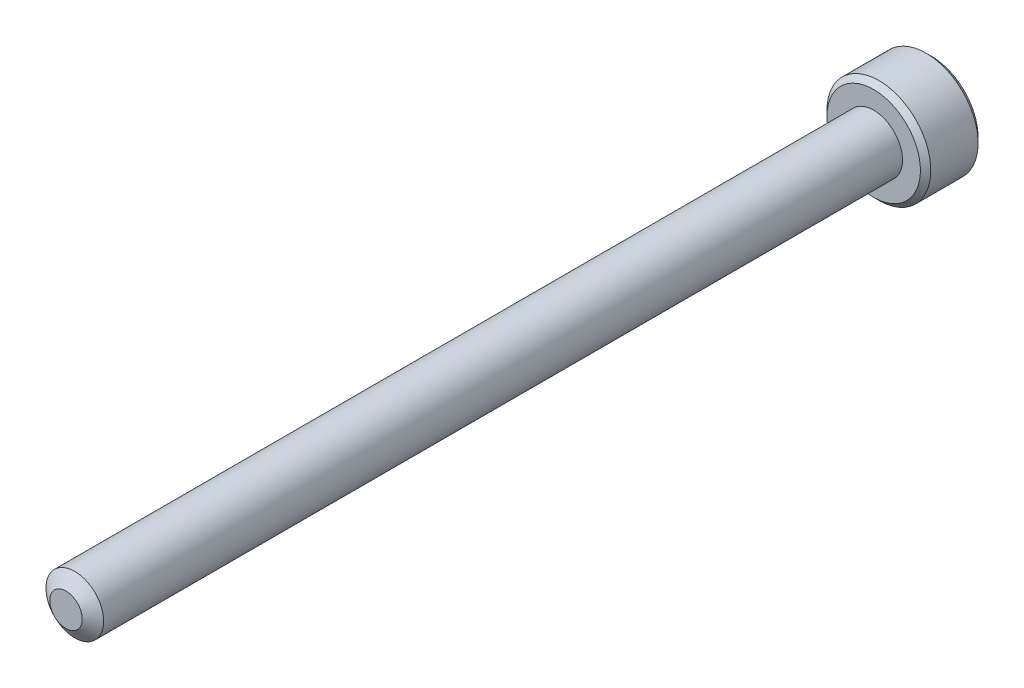
SolidWorks part; units mm, degrees
other "DetailItem1"
ref_plane "Front Plane" through (0, 0, 0) normal (0, 0, 1) x (1, 0, 0)
ref_plane "Top Plane" through (0, 0, 0) normal (0, 1, 0) x (1, 0, 0)
ref_plane "Right Plane" through (0, 0, 0) normal (1, 0, 0) x (0, 0, -1)
sketch "Sketch1" plane through (0, 0, 0) normal (0, 0, 1) x (1, 0, 0)
  circle A0 centre (0, 0) radius 1.25
  dimension "OD" = 2.5
extrude "Extrude1" add sketch "Sketch1" against normal blind 35
sketch "Sketch2" plane through (0, 0, 0) normal (0, 0, 1) x (1, 0, 0)
  circle A0 centre (0, 0) radius 1.25 construction
  circle A1 centre (0, 0) radius 1.25
curve "Helix/Spiral1" [suppressed] pitch 0.45 height 35.45 turns 78.7778 parameters "pitch"=0.45
sketch "Sketch3" plane through (0, 0, 0) normal (1, 0, 0) x (0, 0, -1)
  line L0 (-0.3937, 1.25) -> (-0.225, 0.9577)
  line L1 (-0.225, 0.9577) -> (-0.1688, 0.9577)
  line L2 (-0.1688, 0.9577) -> (0, 1.25)
  line L3 (-0.3937, 1.25) -> (0, 1.25)
  line L4 (-0.1969, 1.25) -> (-0.1969, 0.9577) construction
  line L5 (-0.3094, 1.1039) -> (-0.0844, 1.1039) construction
  line L6 (0, 1.25) -> (0, -1.25) construction
  dimension "D1" = 0.0563
  dimension "D2" = 0.225
  dimension "D3" = 60
sweep "Cut-Sweep1" [suppressed] cut profiles "Sketch3" path "Helix/Spiral1"
sketch "Sketch4" plane through (0, 0, 0) normal (1, 0, 0) x (0, 0, -1)
  line L0 (0.3825, 1.25) -> (0, 0.7037)
  line L1 (0, 0.7037) -> (0, 1.25)
  line L2 (0.3825, 1.25) -> (0, 1.25)
  line L3 (-0.3937, 1.25) -> (0, 1.25) construction
  line L4 (0, 0) -> (7.0209, 0) construction
  dimension "D1" = 55
  dimension "D2" = 0.254
revolve "Cut-Revolve1" cut sketch "Sketch4" angle 360 about L4
sketch "Sketch6" plane through (0, 0, -35) normal (0, 0, -1) x (-1, 0, 0)
  circle A0 centre (0, 0) radius 2.25
  dimension "head dia" = 4.5
extrude "Extrude2" add sketch "Sketch6" along normal blind 2.5
sketch "Sketch7" plane through (0, 0, -37.5) normal (0, 0, -1) x (-1, 0, 0)
  line L1 (0, 1.1547) -> (-1, 0.5774)
  line L2 (-1, 0.5774) -> (-1, -0.5774)
  line L3 (-1, -0.5774) -> (0, -1.1547)
  line L4 (0, -1.1547) -> (1, -0.5774)
  line L5 (1, -0.5774) -> (1, 0.5774)
  line L6 (1, 0.5774) -> (0, 1.1547)
  circle A0 centre (0, 0) radius 1 construction
  dimension "hex dia" = 2
extrude "Cut-Extrude1" cut sketch "Sketch7" against normal blind 1.5
sketch "Sketch8" plane through (0, 0, -37.5) normal (0, 0, -1) x (-1, 0, 0)
  circle A0 centre (0, 0) radius 1.1547
extrude "Cut-Extrude2" cut sketch "Sketch8" against normal through all draft 45
chamfer "Chamfer1" distance 0.225 angle 45 2 edges at (-2.25, 0, -37.5) (-2.25, 0, -35)
sketch "Sketch10" plane through (0, 0, -35) normal (0, 0, 1) x (1, 0, 0)
  circle A1 centre (0, 0) radius 1.25
  circle A2 centre (0, 0) radius 1.25
  dimension "D1" = 0
ref_plane "Plane1" through (0, 0, 0) normal (0, 0, 1) x (1, 0, 0)
extrude "partial thread" [suppressed] add sketch "Sketch10" along normal up to surface (55 mm away) separate body up to plane "Plane1"
chamfer "Chamfer2" [suppressed] distance 0.05 angle 45
combine bodies "Combine1" [suppressed] operation type add bodies to combine 107 108
sketch "Sketch9" plane through (0, 0, 0) normal (1, 0, 0) x (0, 0, -1)
  line L0 (0, 1.25) -> (0, -1.25) construction
  line L1 (1.125, 1.25) -> (1.125, -1.25) construction
  dimension "D1" = 1.125
equation "\"D3@Helix/Spiral1\" = \"screw length@Extrude1\"+\"pitch@Helix/Spiral1\""
equation "\"D1@Sketch3\" = \"pitch@Helix/Spiral1\"*.125"
equation "\"D2@Sketch3\" = \"pitch@Helix/Spiral1\"*.5"
equation "\"D1@Cut-Extrude1\" = \"hex dia@Sketch7\"*.75"
equation "\"D1@Chamfer1\" = \"head dia@Sketch6\"*.05"
equation "\"D1@Sketch9\" = \"pitch@Helix/Spiral1\"*2.5"
equation "\"D1@Chamfer2\"=\"OD@Sketch1\"*.02"
